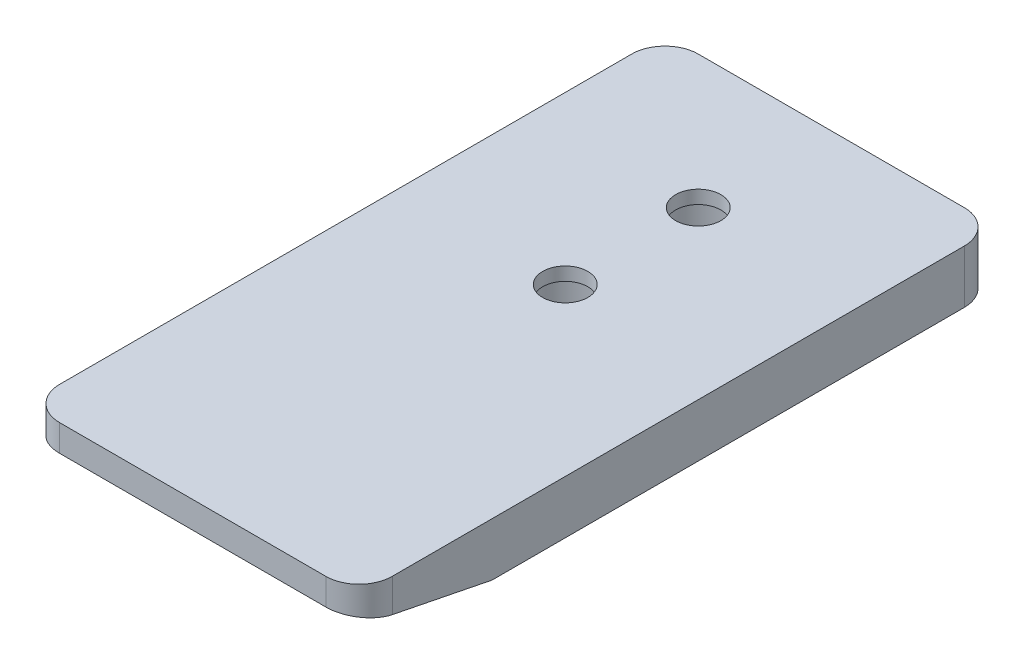
SolidWorks part; units mm, degrees
ref_plane "Front Plane" through (0, 0, 0) normal (0, 0, 1) x (1, 0, 0)
ref_plane "Top Plane" through (0, 0, 0) normal (0, 1, 0) x (1, 0, 0)
ref_plane "Right Plane" through (0, 0, 0) normal (1, 0, 0) x (0, 0, -1)
sketch "Sketch1" plane through (0, 0, 0) normal (0, 1, 0) x (1, 0, 0)
  line L1 (0, 0) -> (25, 0)
  line L2 (0, 0) -> (0, 30)
  line L3 (0, 30) -> (25, 30)
  line L4 (25, 0) -> (25, 30)
  dimension "D1" = 30
  dimension "D2" = 25
extrude "Boss-Extrude1" add sketch "Sketch1" along normal blind 4
hole_wizard "CBORE for M3 SHCS2" positions "Sketch3" profile "Sketch4" counterbore size "M3" standard "ANSI Metric" end condition through all
sketch "Sketch3" plane through (0, 0, 0) normal (0, -1, 0) x (-1, 0, 0)
  line L0 (0, 30) -> (0, 0) construction
  line L1 (0, 0) -> (-25, 0) construction
  line L2 (-12.5, 10) -> (-12.5, 20)
  line L3 (-12.5, 15) -> (0, 15)
  point P0 (-12.5, 20)
  point P8 (-12.5, 0)
  point P31 (-12.5, 10)
  dimension "D1" = 10
sketch "Sketch4" plane through (12.5, 0, -20) normal (1, 0, 0) x (0, 0, -1)
  line L0 (0, 0) -> (0, 4)
  line L1 (0, 4) -> (1.7, 4)
  line L3 (1.7, 4) -> (1.7, 3)
  line L4 (1.7, 3) -> (3.25, 3)
  line L5 (3.25, 3) -> (3.25, 0)
  line L7 (3.25, 0) -> (0, 0)
  line L11 (0, -6.35) -> (0, 107.95) construction
  dimension "Thru Hole Dia." = 3.4
  dimension "Thru Hole Depth" = 4
  dimension "C'Bore Dia." = 6.5
  dimension "C'Bore Depth" = 3
sketch "Sketch5" plane through (0, 0, 0) normal (0, 0, 1) x (1, 0, 0)
  line L4 (0, 0) -> (25, 0)
  line L5 (25, 0) -> (25, 4)
  line L6 (25, 4) -> (0, 4)
  line L7 (0, 4) -> (0, 0)
  line L8 (0, 0) -> (25, 0)
  line L9 (25, 0) -> (25, 4)
  line L10 (25, 4) -> (0, 4)
  line L11 (0, 4) -> (0, 0)
  dimension "D1" = 0
extrude "Boss-Extrude2" add sketch "Sketch5" along normal blind 18
chamfer "Chamfer1" distance 10 distance2 2 1 edges at (12.5, 0, 18) first distance on face at (12.5, 0, -23.25)
fillet "Fillet1" radius 2.5 4 edges at (0, 2, -30) (25, 2, -30) (0, 3, 18) (25, 3, 18)
